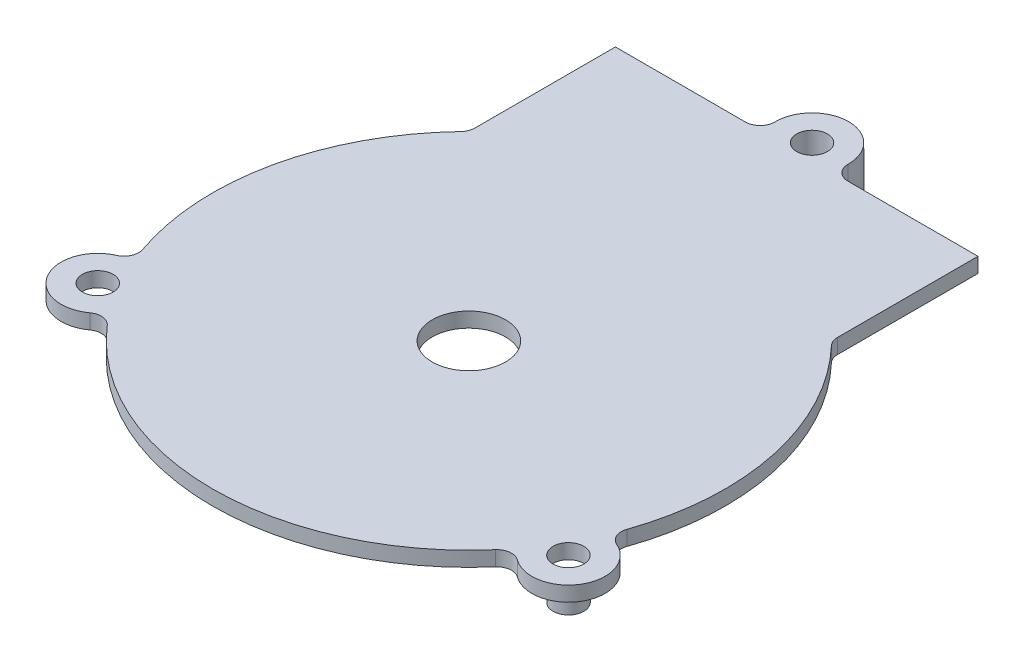
SolidWorks part; units mm, degrees
ref_plane "Front Plane" through (0, 0, 0) normal (0, 0, 1) x (1, 0, 0)
ref_plane "Top Plane" through (0, 0, 0) normal (0, 1, 0) x (1, 0, 0)
ref_plane "Right Plane" through (0, 0, 0) normal (1, 0, 0) x (0, 0, -1)
sketch "Sketch13" plane through (0, 0, 0) normal (0, 1, 0) x (1, 0, 0)
  circle A0 centre (0, 0) radius 35
extrude "Boss-Extrude3" add sketch "Sketch13" along normal blind 2.032
sketch "Sketch14" plane through (0, 2.032, 0) normal (0, 1, 0) x (1, 0, 0)
  line L0 (-24.7478, 24.7497) -> (24.7477, 24.7498)
  line L1 (-24.7478, 24.7497) -> (-24.7479, 44.7452)
  line L2 (24.7477, 24.7498) -> (24.7476, 44.7454)
  line L3 (-24.7479, 44.7452) -> (24.7476, 44.7454)
  line L4 (0, 0) -> (60.4611, -34.8658) construction
  line L5 (0, 0) -> (-56.6044, -32.6614) construction
  line L7 (-3.939, 44.1714) -> (-8.8985, 44.1714)
  line L8 (-3.939, 44.1714) -> (-3.939, 47.547)
  line L9 (-3.939, 47.547) -> (-8.8985, 47.547)
  line L10 (-8.8985, 44.1714) -> (-8.8985, 47.547)
  arc A0 (0, 35) -> (-24.7478, 24.7497) centre (0, 0) ccw construction
  circle A1 centre (0, 0) radius 35 construction
  arc A2 (0, 35) -> (-30.3109, -17.4999) centre (0, 0) ccw construction
  arc A3 (0, 35) -> (30.3118, -17.4984) centre (0, 0) ccw
  arc A4 (0, 35) -> (24.7477, 24.7498) centre (0, 0) ccw construction
  circle A5 centre (32.1365, -18.5413) radius 2.1017
  circle A6 centre (32.1365, -18.5413) radius 4.9951
  circle A7 centre (-32.1465, -18.5162) radius 2.0981
  circle A8 centre (-32.1465, -18.5162) radius 4.9995
extrude "Boss-Extrude4" add sketch "Sketch14" against normal up to surface (2.032 mm away) contours L0 L1 L3 L2 up to face at (0, 0, 35)
sketch "Sketch15" plane through (0, 2.032, 0) normal (0, 1, 0) x (1, 0, 0)
  line L0 (0, 0) -> (0, 62.3966) construction
  line L1 (-0.0001, 44.7453) -> (0, 46.8414) construction
  line L2 (-24.7479, 44.7452) -> (24.7476, 44.7454) construction
  circle A0 centre (0, 46.8414) radius 2.0961
  circle A1 centre (0, 46.8414) radius 4.996
extrude "Boss-Extrude11" add sketch "Sketch15" against normal blind 5.588 contours A1 | A0
extrude "Boss-Extrude12" add sketch "Sketch14<6>" against normal up to surface (2.032 mm away) contours A6 up to face at (0, 0, -27.6385)
sketch "Sketch14<6>" plane through (0, 2.032, 0) normal (0, 1, 0) x (1, 0, 0) same geometry as "Sketch14"
extrude "Boss-Extrude14" add sketch "Sketch14<8>" against normal through all contours L0 A5 region at (32.1365, 2.032, 18.5413)
sketch "Sketch14<8>" plane through (0, 2.032, 0) normal (0, 1, 0) x (1, 0, 0) same geometry as "Sketch14"
hole_wizard "Ø4.2 (4.2) Diameter Hole1" positions "Sketch22" profile "Sketch23" hole size "Ø4.2" standard "ANSI Metric" end condition through all
sketch "Sketch22" plane through (0, 2.032, 0) normal (0, 1, 0) x (1, 0, 0)
  point P0 (32.1248, -18.5356)
sketch "Sketch23" plane through (32.1248, 2.032, 18.5356) normal (1, 0, 0) x (0, 0, 1)
  line L0 (0, 0) -> (0, 5.588)
  line L1 (0, 5.588) -> (2.1, 5.588)
  line L2 (2.1, 5.588) -> (2.1, 0)
  line L5 (2.1, 0) -> (0, 0)
  line L11 (0, -6.35) -> (0, 107.95) construction
  dimension "Thru Hole Dia." = 4.2
  dimension "Thru Hole Depth" = 5.588
extrude "Boss-Extrude15" add sketch "Sketch14<11>" against normal up to surface (2.032 mm away) contours A8 up to face at (5.9749, 0, -20.0206)
sketch "Sketch14<11>" plane through (0, 2.032, 0) normal (0, 1, 0) x (1, 0, 0) same geometry as "Sketch14"
hole_wizard "Ø4.2 (4.2) Diameter Hole2" positions "Sketch26" profile "Sketch27" hole size "Ø4.2" standard "ANSI Metric" end condition through all
sketch "Sketch26" plane through (0, 2.032, 0) normal (0, 1, 0) x (1, 0, 0)
  point P0 (-32.148, -18.5088)
  point P2 (-32.148, -18.5088)
sketch "Sketch27" plane through (-32.148, 2.032, 18.5088) normal (1, 0, 0) x (0, 0, 1)
  line L0 (0, 0) -> (0, 5.588)
  line L1 (0, 5.588) -> (2.1, 5.588)
  line L2 (2.1, 5.588) -> (2.1, 0)
  line L5 (2.1, 0) -> (0, 0)
  line L11 (0, -6.35) -> (0, 107.95) construction
  dimension "Thru Hole Dia." = 4.2
  dimension "Thru Hole Depth" = 5.588
fillet "Fillet4" radius 2 1 edges at (-24.7478, 1.016, -24.7497)
fillet "Fillet6" radius 2 1 edges at (-32.2839, 1.016, 13.5185)
fillet "Fillet7" radius 2 1 edges at (-27.8924, 1.016, 21.1427)
fillet "Fillet8" radius 2 1 edges at (27.8812, 1.016, 21.1574)
fillet "Fillet9" radius 2 1 edges at (32.2715, 1.016, 13.548)
fillet "Fillet10" radius 2 1 edges at (24.7477, 1.016, -24.7498)
fillet "Fillet11" radius 2 1 edges at (4.535, 1.016, -44.7453)
fillet "Fillet12" radius 2 1 edges at (-4.535, 1.016, -44.7453)
sketch "Sketch28" plane through (0, 2.032, 0) normal (0, 1, 0) x (1, 0, 0)
  circle A0 centre (0, 0) radius 5
extrude "Cut-Extrude1" cut sketch "Sketch28" against normal up to surface (2.032 mm away) up to face at (-32.148, 0, 20.6088)
